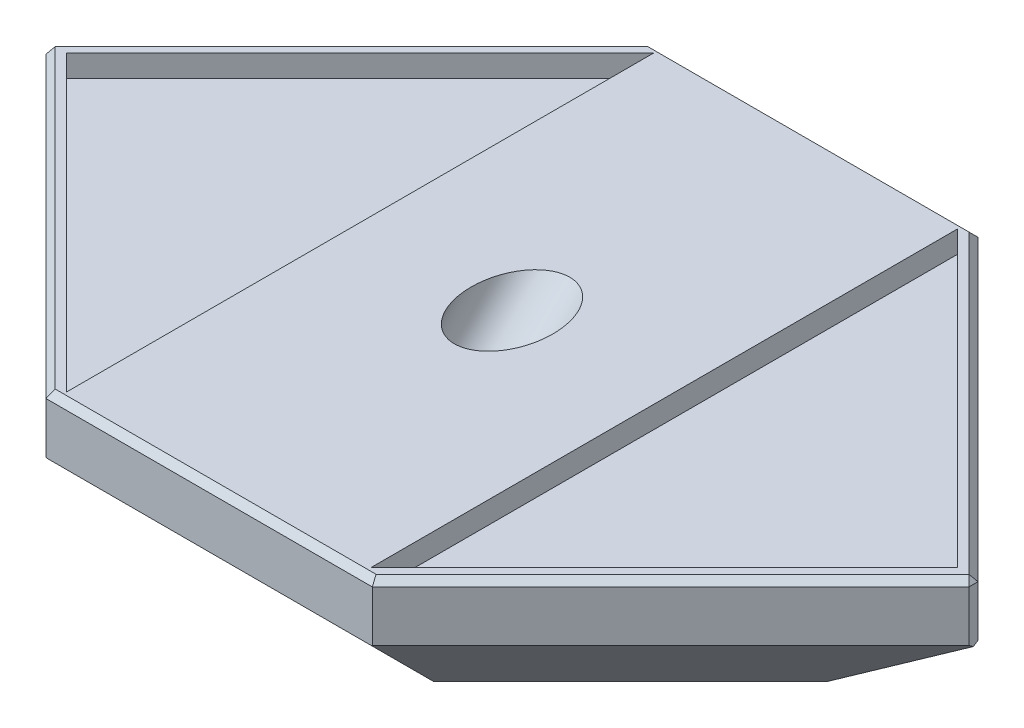
SolidWorks part; units mm, degrees
note: The reader was unsure of these and kept them because the rebuilt part matched: shared geometry of "Sketch5<3>".
ref_plane "Front Plane" through (0, 0, 0) normal (0, 0, 1) x (1, 0, 0)
ref_plane "Top Plane" through (0, 0, 0) normal (0, 1, 0) x (1, 0, 0)
ref_plane "Right Plane" through (0, 0, 0) normal (1, 0, 0) x (0, 0, -1)
sketch "Sketch1" plane through (0, 0, 0) normal (0, 1, 0) x (1, 0, 0)
  line L4 (-25.4, 47.1463) -> (25.4, 47.1463)
  line L5 (25.4, 47.1463) -> (72.5463, 0)
  line L6 (72.5463, 0) -> (25.4, -47.1463)
  line L7 (25.4, -47.1463) -> (-25.4, -47.1463)
  line L8 (-25.4, -47.1463) -> (-72.5463, 0)
  line L9 (-72.5463, 0) -> (-25.4, 47.1463)
  line L10 (0, 47.1463) -> (0, -47.1463) construction
  point P9 (0, 0)
  dimension "D1" = 66.675
  dimension "D2" = 50.8
extrude "Boss-Extrude1" add sketch "Sketch1" along normal blind 76.2
ref_plane "Plane1" through (0, 14.5268, 14.5268) normal (0, 0.7071, 0.7071) x (-1, 0, 0)
ref_plane "Plane2" through (0, 10.0367, 10.0367) normal (0, 0.7071, 0.7071) x (-1, 0, 0)
other "SurfaceCut1"
ref_plane "Plane3" through (0, 14.5268, -14.5268) normal (0, 0.7071, -0.7071) x (1, 0, 0)
ref_plane "Plane4" through (0, 10.0367, -10.0367) normal (0, 0.7071, -0.7071) x (1, 0, 0)
other "SurfaceCut2"
ref_plane "Plane5" through (0, 50.8, 0) normal (0, 1, 0) x (1, 0, 0)
other "SurfaceCut3"
chamfer "Chamfer1" distance 16.51 angle 45 4 edges at (-57.183, 50.8, 15.3633) (-57.183, 50.8, -15.3633) (57.183, 50.8, 15.3633) (57.183, 50.8, -15.3633)
chamfer "Chamfer2" distance 1 angle 45 8 edges at (-72.5463, 71.755, 0) (72.5463, 71.755, 0) (48.9732, 76.2, 23.5732) (0, 76.2, 47.1463) (-48.9732, 76.2, 23.5732) (-48.9732, 76.2, -23.5732) (0, 76.2, -47.1463) (48.9732, 76.2, -23.5732)
sketch "Sketch2" plane through (0, 76.2, 0) normal (0, 1, 0) x (1, 0, 0)
  line L3 (-23.6828, 45.6816) -> (-69.3644, 0)
  line L4 (-69.3644, 0) -> (-23.6828, -45.6816)
  line L5 (-23.6828, -45.6816) -> (-23.6828, 45.6816)
  line L6 (-23.6828, 45.6816) -> (-69.3644, 0)
  line L7 (-69.3644, 0) -> (-23.6828, -45.6816)
  line L8 (-23.6828, -45.6816) -> (-23.6828, 45.6816)
  line L9 (69.3644, 0) -> (23.6828, 45.6816)
  line L10 (23.6827, -45.6816) -> (69.3644, 0)
  line L11 (23.6828, 45.6816) -> (23.6827, -45.6816)
  line L12 (69.3644, 0) -> (23.6828, 45.6816)
  line L13 (23.6827, -45.6816) -> (69.3644, 0)
  line L14 (23.6828, 45.6816) -> (23.6827, -45.6816)
  dimension "D1" = 0.25
  dimension "D2" = 0.25
extrude "Cut-Extrude1" cut sketch "Sketch2" against normal blind 3.425
sketch "Sketch5" plane through (0, 10.0367, -10.0367) normal (0, 0.7071, -0.7071) x (1, 0, 0)
  line L0 (0, -21.2511) -> (0, -86.5119) construction
  line L6 (-24.9858, -86.5119) -> (24.9858, -86.5119)
  line L7 (24.9858, -86.5119) -> (71.1321, -53.8815)
  line L8 (71.1321, -53.8815) -> (24.9858, -21.2511)
  line L9 (24.9858, -21.2511) -> (-24.9858, -21.2511)
  line L10 (-24.9858, -21.2511) -> (-71.1321, -53.8815)
  line L11 (-71.1321, -53.8815) -> (-24.9858, -86.5119)
  line L12 (-24.9858, -86.5119) -> (24.9858, -86.5119) construction
  line L13 (24.9858, -86.5119) -> (71.1321, -53.8815) construction
  line L14 (71.1321, -53.8815) -> (24.9858, -21.2511) construction
  line L15 (24.9858, -21.2511) -> (-24.9858, -21.2511) construction
  line L16 (-24.9858, -21.2511) -> (-71.1321, -53.8815) construction
  line L17 (-71.1321, -53.8815) -> (-24.9858, -86.5119) construction
  circle A0 centre (0, -53.8815) radius 1.905
  circle A1 centre (0, -53.8815) radius 3.81
  dimension "D2" = 3.81
  dimension "D3" = 7.62
  dimension "D1" = 0
extrude "Cut-Extrude2" cut sketch "Sketch5" along normal through all contours A0
ref_plane "Plane6" through (0, 36.9775, -36.9775) normal (0, 0.7071, -0.7071) x (1, 0, 0)
sketch "Sketch6" plane through (0, 36.9775, -36.9775) normal (0, 0.7071, -0.7071) x (1, 0, 0)
  line L0 (0, -86.5119) -> (0, -21.2511) construction
  line L6 (-24.9858, -86.5119) -> (24.9858, -86.5119)
  line L7 (24.9858, -86.5119) -> (71.1321, -53.8815)
  line L8 (71.1321, -53.8815) -> (24.9858, -21.2511)
  line L9 (24.9858, -21.2511) -> (-24.9858, -21.2511)
  line L10 (-24.9858, -21.2511) -> (-71.1321, -53.8815)
  line L11 (-71.1321, -53.8815) -> (-24.9858, -86.5119)
  line L12 (-24.9858, -86.5119) -> (24.9858, -86.5119) construction
  line L13 (24.9858, -86.5119) -> (71.1321, -53.8815) construction
  line L14 (71.1321, -53.8815) -> (24.9858, -21.2511) construction
  line L15 (24.9858, -21.2511) -> (-24.9858, -21.2511) construction
  line L16 (-24.9858, -21.2511) -> (-71.1321, -53.8815) construction
  line L17 (-71.1321, -53.8815) -> (-24.9858, -86.5119) construction
  circle A0 centre (0, -53.8815) radius 6.35
  dimension "D2" = 12.7
  dimension "D1" = 0
extrude "Cut-Extrude3" cut sketch "Sketch6" against normal blind 12.7 and the other way through all
extrude "Cut-Extrude4" cut sketch "Sketch5<3>" along normal blind 12.7
sketch "Sketch5<3>" plane through (0, 10.0367, -10.0367) normal (0, 0.7071, -0.7071) x (1, 0, 0) same geometry as "Sketch5"
